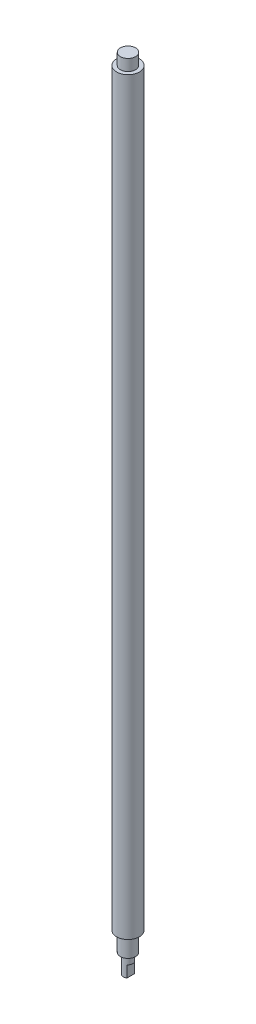
SolidWorks part; units mm, degrees
ref_plane "Front Plane" through (0, 0, 0) normal (0, 0, 1) x (1, 0, 0)
ref_plane "Top Plane" through (0, 0, 0) normal (0, 1, 0) x (1, 0, 0)
ref_plane "Right Plane" through (0, 0, 0) normal (1, 0, 0) x (0, 0, -1)
sketch "Sketch1" plane through (0, 0, 0) normal (0, 1, 0) x (1, 0, 0)
  line L0 (1.5, 2) -> (1.5, -2)
  circle A0 centre (0, 0) radius 6
  circle A1 centre (0, 0) radius 4
  circle A2 centre (0, 0) radius 2.5
  dimension "D1" = 12
  dimension "D2" = 8
  dimension "D3" = 5
  dimension "D4" = 1.5
extrude "Boss-Extrude1" add sketch "Sketch1" along normal blind 420 contours L0 A2 | L0 A2 | A1 A2 region at (1.9078, 0, 0) region at (-0.3167, 0, 0) region at (-3.8869, 0, 0)
extrude "Boss-Extrude2" add sketch "Sketch1<3>" along normal blind 414 contours A0 A1 region at (-5.8303, 0, 0)
sketch "Sketch1<3>" plane through (0, 0, 0) normal (0, 1, 0) x (1, 0, 0) same geometry as "Sketch1"
extrude "Cut-Extrude1" cut sketch "Sketch1<4>" along normal blind 20 contours A0 A1 region at (-5.8303, 0, 0)
sketch "Sketch1<4>" plane through (0, 0, 0) normal (0, 1, 0) x (1, 0, 0) same geometry as "Sketch1"
extrude "Cut-Extrude2" cut sketch "Sketch1<5>" along normal blind 10 contours A1 A2 region at (-3.8869, 0, 0)
sketch "Sketch1<5>" plane through (0, 0, 0) normal (0, 1, 0) x (1, 0, 0) same geometry as "Sketch1"
extrude "Cut-Extrude3" cut sketch "Sketch1<6>" along normal blind 6 contours L0 A2 region at (1.9078, 0, 0)
sketch "Sketch1<6>" plane through (0, 0, 0) normal (0, 1, 0) x (1, 0, 0) same geometry as "Sketch1"
